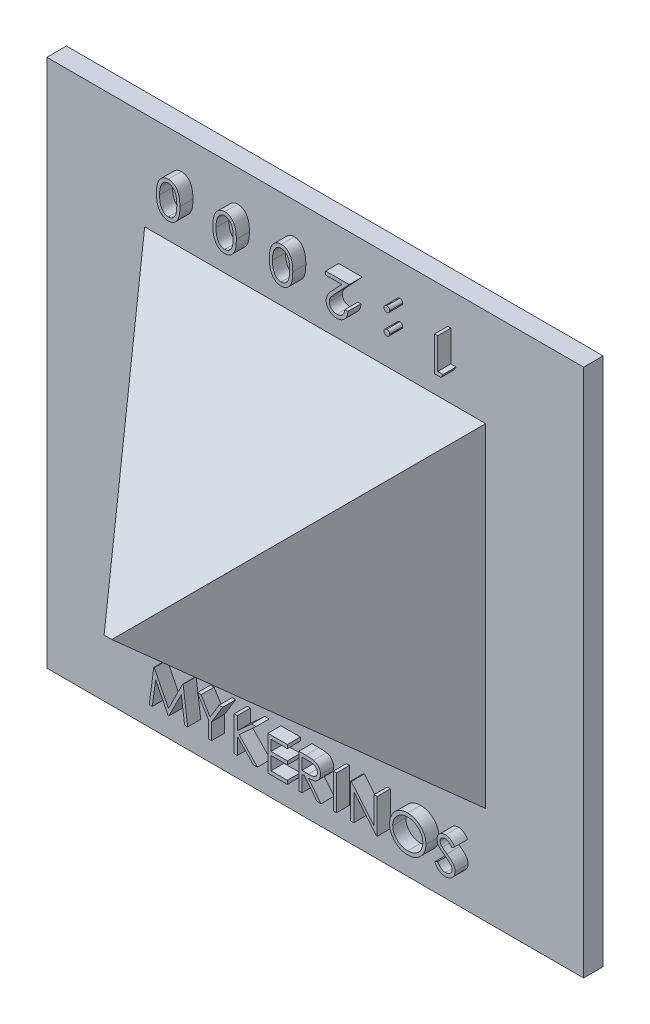
SolidWorks part; units mm, degrees
ref_plane "Plan de face" through (0, 0, 0) normal (0, 0, 1) x (1, 0, 0)
ref_plane "Plan de dessus" through (0, 0, 0) normal (0, 1, 0) x (1, 0, 0)
ref_plane "Plan de droite" through (0, 0, 0) normal (1, 0, 0) x (0, 0, -1)
sketch "Esquisse1" plane through (0, 0, 0) normal (0, 0, 1) x (1, 0, 0)
  line L1 (0, 0) -> (52.275, 0)
  line L2 (0, 0) -> (0, 51.0975)
  line L3 (0, 51.0975) -> (52.275, 51.0975)
  line L4 (52.275, 0) -> (52.275, 51.0975)
  dimension "D1" = 52.275
  dimension "D2" = 51.0975
extrude "Boss.-Extru.1" add sketch "Esquisse1" along normal blind 50 draft 38.8
sketch "Esquisse3" plane through (0, 0, 0) normal (0, 0, -1) x (-1, 0, 0)
  line L8 (15, -15) -> (15, 66.0975)
  line L9 (15, 66.0975) -> (-67.275, 66.0975)
  line L10 (-67.275, 66.0975) -> (-67.275, -15)
  line L11 (-67.275, -15) -> (15, -15)
  line L12 (15, -15) -> (15, 66.0975)
  line L13 (15, 66.0975) -> (-67.275, 66.0975)
  line L14 (-67.275, 66.0975) -> (-67.275, -15)
  line L15 (-67.275, -15) -> (15, -15)
  dimension "D1" = 15
extrude "Boss.-Extru.3" add sketch "Esquisse3" along normal blind 3 separate body
sketch "Esquisse2" plane through (0, 0, -3) normal (0, 0, -1) x (-1, 0, 0)
  line L0 (0, 0) -> (-52.275, 0) construction
  line L1 (0, 51.0975) -> (0, 0) construction
  circle A0 centre (-26.1375, 25.5487) radius 23.25
  point P5 (-26.1375, 0)
  point P8 (0, 25.5487)
  dimension "D1" = 46.5
extrude "Boss.-Extru.2" [suppressed] add sketch "Esquisse2" along normal blind 30
sketch "Esquisse4" plane through (0, 0, 0) normal (0, 0, 1) x (1, 0, 0)
  line L0 (2.2826, -10) -> (49.9924, -10) construction
  line L1 (3.5262, 61.0975) -> (48.7488, 61.0975) construction
  line L2 (0, 0) -> (52.275, 0) construction
  line L3 (67.275, -15) -> (-15, -15) construction
  line L4 (52.275, 51.0975) -> (0, 51.0975) construction
  line L5 (-15, 66.0975) -> (67.275, 66.0975) construction
  text T0 "MYKERINOS" font "Century Gothic" height in points 20
  text T1 "1:2000" font "Century Gothic" height in points 20
  point P6 (26.1375, 0)
  point P7 (26.1375, -10)
  point P12 (26.1375, 51.0975)
  point P13 (26.1375, 61.0975)
  dimension "D1" = 5
  dimension "D2" = 5
extrude "Boss.-Extru.4" add sketch "Esquisse4" along normal blind 2
